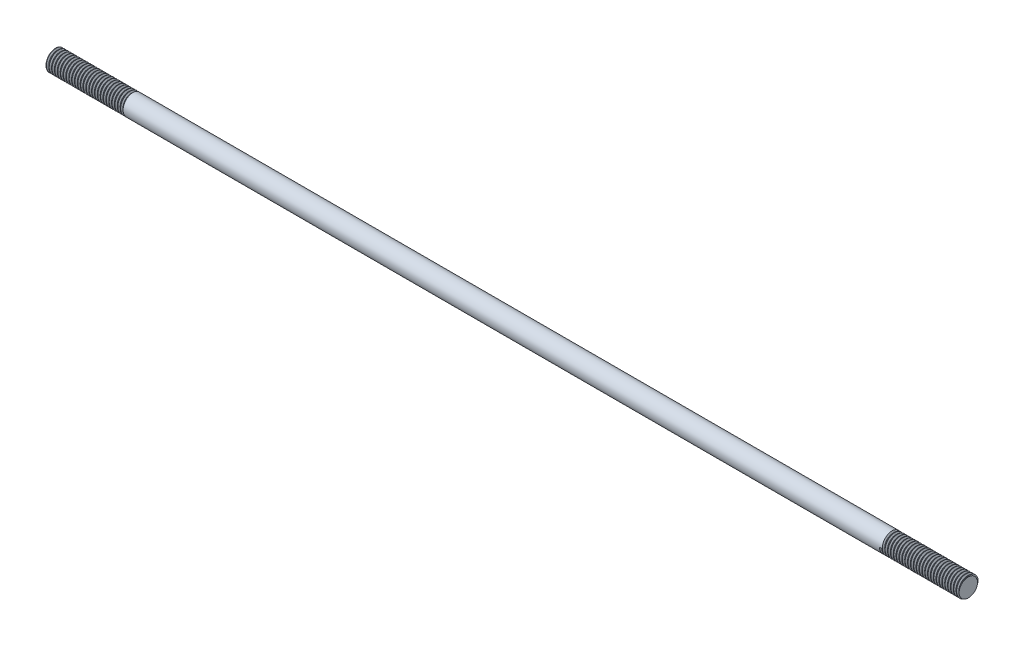
SolidWorks part; units mm, degrees
ref_plane "Front Plane" through (0, 0, 0) normal (0, 0, 1) x (1, 0, 0)
ref_plane "Top Plane" through (0, 0, 0) normal (0, 1, 0) x (1, 0, 0)
ref_plane "Right Plane" through (0, 0, 0) normal (1, 0, 0) x (0, 0, -1)
sketch "Sketch1" plane through (0, 0, 0) normal (1, 0, 0) x (0, 0, -1)
  circle A0 centre (0, 0) radius 3.5
  dimension "D1" = 7
extrude "Boss-Extrude1" add sketch "Sketch1" along normal blind 320
thread "Thread1" pitch 1 method cut profile "Thread Profile1" start angle 0, offset 1, length 0, pitch 1, diameter 7
ref_plane "Plane1" through (-1, 0, -3.5) normal (0, -1, 0) x (0, 0, -1)
sketch "Thread Profile1" plane through (-1, 0, -3.5) normal (0, -1, 0) x (0, 0, -1)
  line L0 (0, 0) -> (0, 1) construction
  line L11 (0, 0) -> (0, 0.875)
  line L12 (0, 0.875) -> (-0.5413, 0.5625)
  line L13 (-0.5413, 0.5625) -> (-0.5413, 0.3125)
  line L15 (-0.5413, 0.3125) -> (0, 0)
  line L17 (-0.5413, 0.4375) -> (0, 0.4375) construction
  point P2 (0, 0)
  dimension "Pitch" = 1
  dimension "Profile_Angle" = 60
  dimension "Profile_Land" = 0.25
  dimension "Profile_Height" = 0.5413
thread "Thread2" pitch 1 method cut profile "Thread Profile2" start angle 0, offset 1, length 0, pitch 1, diameter 7
ref_plane "Plane2" through (321, 0, 3.5) normal (0, -1, 0) x (0, 0, 1)
sketch "Thread Profile2" plane through (321, 0, 3.5) normal (0, -1, 0) x (0, 0, 1)
  line L0 (0, 0) -> (0, 1) construction
  line L11 (0, 0) -> (0, 0.875)
  line L12 (0, 0.875) -> (-0.5413, 0.5625)
  line L13 (-0.5413, 0.5625) -> (-0.5413, 0.3125)
  line L15 (-0.5413, 0.3125) -> (0, 0)
  line L17 (-0.5413, 0.4375) -> (0, 0.4375) construction
  point P2 (0, 0)
  dimension "Pitch" = 1
  dimension "Profile_Angle" = 60
  dimension "Profile_Land" = 0.25
  dimension "Profile_Height" = 0.5413
